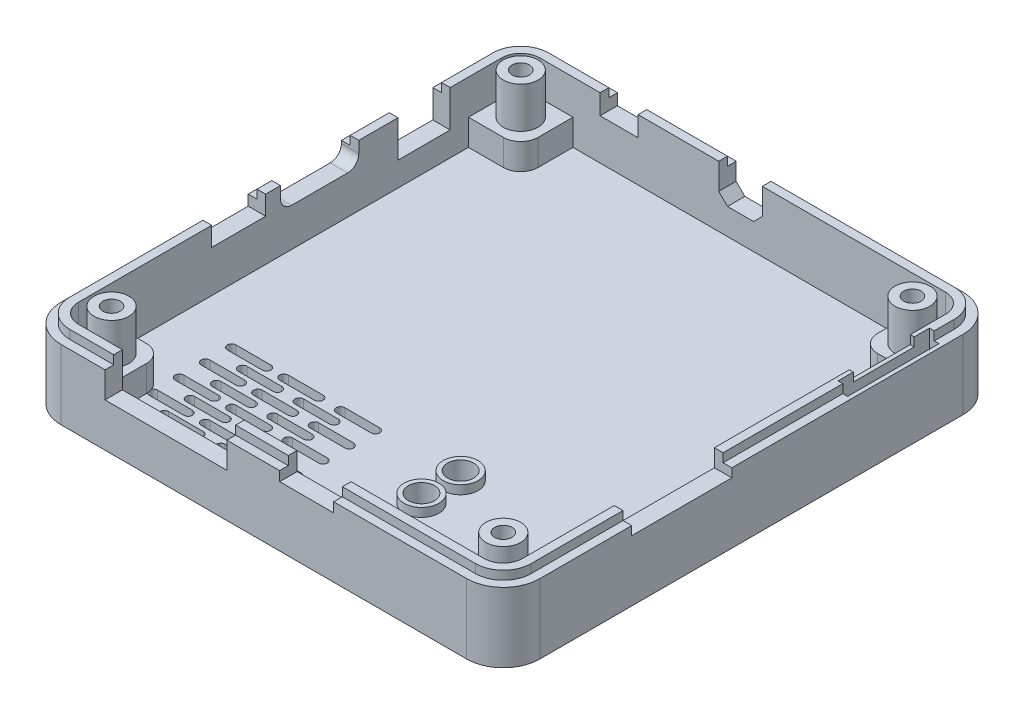
SolidWorks part; units mm, degrees
ref_plane "Front Plane" through (0, 0, 0) normal (0, 0, 1) x (1, 0, 0)
ref_plane "Top Plane" through (0, 0, 0) normal (0, 1, 0) x (1, 0, 0)
ref_plane "Right Plane" through (0, 0, 0) normal (1, 0, 0) x (0, 0, -1)
sketch "Sketch1" plane through (0, 0, 0) normal (0, 1, 0) x (1, 0, 0)
  line L17 (-23.3, 27.5) -> (23.3, 27.5)
  line L18 (-23.3, 26.5) -> (23.3, 26.5)
  line L26 (-25.5, 24.3) -> (-25.5, -24.3)
  line L27 (-23.3, -26.5) -> (23.3, -26.5)
  line L28 (25.5, 24.3) -> (25.5, -24.3)
  line L29 (-25.5, 26.5) -> (25.5, -26.5) construction
  line L30 (-25.5, -26.5) -> (25.5, 26.5) construction
  line L31 (26.5, 24.3) -> (26.5, -24.3)
  line L32 (-23.3, -27.5) -> (23.3, -27.5)
  line L33 (-26.5, 24.3) -> (-26.5, -24.3)
  line L34 (-23.3, 28.5) -> (23.3, 28.5)
  line L35 (27.5, 24.3) -> (27.5, -24.3)
  line L36 (-23.3, -28.5) -> (23.3, -28.5)
  line L37 (-27.5, 24.3) -> (-27.5, -24.3)
  line L38 (-19.5, 26.5) -> (-19.5, 22.5)
  line L39 (-25.5, -20.5) -> (-21.5, -20.5)
  line L40 (19.5, -26.5) -> (19.5, -22.5)
  line L41 (-25.5, 20.5) -> (-21.5, 20.5)
  line L42 (-19.5, -22.5) -> (-19.5, -26.5)
  line L43 (21.5, -20.5) -> (25.5, -20.5)
  line L44 (19.5, 22.5) -> (19.5, 26.5)
  line L45 (21.5, 20.5) -> (25.5, 20.5)
  arc A32 (25.5, -24.3) -> (23.3, -26.5) centre (23.3, -24.3) cw
  arc A33 (-23.3, -26.5) -> (-25.5, -24.3) centre (-23.3, -24.3) cw
  arc A34 (25.5, 24.3) -> (23.3, 26.5) centre (23.3, 24.3) ccw
  arc A35 (-23.3, 26.5) -> (-25.5, 24.3) centre (-23.3, 24.3) ccw
  arc A36 (26.5, 24.3) -> (23.3, 27.5) centre (23.3, 24.3) ccw
  arc A37 (26.5, -24.3) -> (23.3, -27.5) centre (23.3, -24.3) cw
  arc A38 (-23.3, -27.5) -> (-26.5, -24.3) centre (-23.3, -24.3) cw
  arc A39 (-23.3, 27.5) -> (-26.5, 24.3) centre (-23.3, 24.3) ccw
  arc A40 (27.5, 24.3) -> (23.3, 28.5) centre (23.3, 24.3) ccw
  arc A41 (27.5, -24.3) -> (23.3, -28.5) centre (23.3, -24.3) cw
  arc A42 (-23.3, -28.5) -> (-27.5, -24.3) centre (-23.3, -24.3) cw
  arc A43 (-23.3, 28.5) -> (-27.5, 24.3) centre (-23.3, 24.3) ccw
  circle A44 centre (-22.5, 23.5) radius 1
  circle A45 centre (22.5, 23.5) radius 1
  circle A46 centre (-22.5, -23.5) radius 1
  circle A47 centre (22.5, -23.5) radius 1
  arc A48 (19.5, 22.5) -> (21.5, 20.5) centre (21.5, 22.5) ccw
  arc A49 (21.5, -20.5) -> (19.5, -22.5) centre (21.5, -22.5) ccw
  arc A50 (-19.5, -22.5) -> (-21.5, -20.5) centre (-21.5, -22.5) ccw
  arc A51 (-19.5, 22.5) -> (-21.5, 20.5) centre (-21.5, 22.5) cw
  point P0 (0, 0)
  point P63 (19.5, 20.5)
  point P66 (19.5, -20.5)
  point P70 (-19.5, -20.5)
  point P73 (-19.5, 20.5)
  dimension "D3" = 2.2
  dimension "D14" = 3
  dimension "D17" = 3
  dimension "D18" = 2
  dimension "D19" = 2
  dimension "D28" = 6
  dimension "D10" = 3
  dimension "D11" = 3
  dimension "D12" = 3
  dimension "D13" = 3
  dimension "D15" = 3
  dimension "D16" = 3
  dimension "D20" = 2
  dimension "D21" = 2
  dimension "D30" = 2
  dimension "D1" = 51
  dimension "D2" = 53
  dimension "D4" = 1
  dimension "D5" = 1
  dimension "D6" = 53
  dimension "D7" = 55
  dimension "D8" = 55
  dimension "D9" = 57
  dimension "D22" = 6
  dimension "D23" = 6
  dimension "D24" = 6
  dimension "D25" = 6
  dimension "D26" = 6
  dimension "D27" = 6
  dimension "D29" = 6
extrude "Boss-Extrude1" add sketch "Sketch1" along normal blind 8 contours L34 A43 L37 A42 L36 A41 L35 A40 A39 L17 A36 L31 A37 L32 A38 L33 region at (0, 0, -27.7079)
extrude "Boss-Extrude2" add sketch "Sketch1<3>" along normal blind 9 contours L17 A39 L33 A38 L32 A37 L31 A36 A35 L18 A34 L28 A32 L27 A33 L26 region at (0, 0, -26.7362)
sketch "Sketch1<3>" plane through (0, 0, 0) normal (0, 1, 0) x (1, 0, 0) same geometry as "Sketch1"
extrude "Boss-Extrude3" add sketch "Sketch1<4>" along normal blind 2 contours L38 A51 L41 L26 L39 A50 L42 L27 L40 A49 L43 L28 L45 A48 L44 L18 region at (0, 0, 0)
sketch "Sketch1<4>" plane through (0, 0, 0) normal (0, 1, 0) x (1, 0, 0) same geometry as "Sketch1"
extrude "Boss-Extrude4" add sketch "Sketch1<5>" along normal blind 5 contours A51 L38 L18 A35 L26 L41 A44 | L42 A50 L39 L26 A33 L27 A46 | L43 A49 L40 L27 A32 L28 A47 | L44 A48 L45 L28 A34 L18 A45 | A44 | A45 | A47 | A46 region at (-21.4, 0, -26.4151) region at (21.4, 0, -26.4151) region at (-23.5, 0, 20.5849) region at (25.4151, 0, 22.4)
sketch "Sketch1<5>" plane through (0, 0, 0) normal (0, 1, 0) x (1, 0, 0) same geometry as "Sketch1"
sketch "Sketch2" plane through (0, 5, 0) normal (0, 1, 0) x (1, 0, 0)
  circle A0 centre (-22.5, 23.5) radius 1
  circle A1 centre (22.5, 23.5) radius 1
  circle A2 centre (22.5, -23.5) radius 1
  circle A3 centre (-22.5, -23.5) radius 1
  circle A4 centre (-22.5, -23.5) radius 2
  circle A5 centre (22.5, -23.5) radius 2
  circle A6 centre (22.5, 23.5) radius 2
  circle A7 centre (-22.5, 23.5) radius 2
  dimension "D1" = 2
  dimension "D2" = 4
  dimension "D3" = 2
  dimension "D4" = 4
  dimension "D5" = 2
  dimension "D6" = 4
  dimension "D7" = 2
  dimension "D8" = 4
extrude "Boss-Extrude5" add sketch "Sketch2" along normal blind 4.7
sketch "Sketch3" plane through (-27.5, 0, 0) normal (-1, 0, 0) x (0, 0, 1)
  line L0 (-24.3, 9) -> (24.3, 9) construction
  line L1 (-18.4, 9) -> (-12.4, 9)
  line L2 (-18.4, 9) -> (-18.4, 4.78)
  line L3 (-18.4, 4.78) -> (-12.4, 4.78)
  line L4 (-12.4, 9) -> (-12.4, 4.78)
  line L6 (-7.9, 9) -> (1.1, 9)
  line L7 (-7.9, 9) -> (-7.9, 7.68)
  line L8 (-6.62, 6.4) -> (-0.18, 6.4)
  line L9 (1.1, 9) -> (1.1, 7.68)
  line L10 (2.8, 9) -> (9, 9)
  line L11 (2.8, 9) -> (2.8, 6.8)
  line L12 (2.8, 6.8) -> (9, 6.8)
  line L13 (9, 9) -> (9, 6.8)
  line L14 (28.5, 8) -> (28.5, 0) construction
  line L15 (-28.5, 8) -> (-28.5, 0) construction
  arc A0 (1.1, 7.68) -> (-0.18, 6.4) centre (-0.18, 7.68) cw
  arc A1 (-6.62, 6.4) -> (-7.9, 7.68) centre (-6.62, 7.68) cw
  point P20 (1.1, 6.4)
  point P23 (-7.9, 6.4)
  dimension "D11" = 1.28
  dimension "D1" = 6
  dimension "D2" = 4.22
  dimension "D3" = 4.5
  dimension "D4" = 9
  dimension "D5" = 1.7
  dimension "D6" = 6.2
  dimension "D7" = 2.6
  dimension "D8" = 2.2
  dimension "D9" = 27.4
  dimension "D10" = 20.6
extrude "Cut-Extrude1" cut sketch "Sketch3" against normal blind 2
sketch "Sketch5" plane through (0, 0, -28.5) normal (0, 0, -1) x (-1, 0, 0)
  line L0 (0, 0) -> (0, 21.9509) construction
  line L1 (23.3, 9) -> (-23.3, 9) construction
  line L2 (1.75, 5) -> (-1.25, 5)
  line L3 (2.75, 6) -> (2.75, 9)
  line L4 (2.75, 9) -> (-2.25, 9)
  line L5 (-2.25, 6) -> (-2.25, 9)
  line L6 (2.75, 5) -> (-2.25, 9) construction
  line L7 (2.75, 9) -> (-2.25, 5) construction
  line L8 (-1.25, 5) -> (-2.25, 6)
  line L9 (2.75, 6) -> (1.75, 5)
  line L10 (27.5, 8) -> (27.5, 0) construction
  line L11 (12.02, 9) -> (16.38, 9)
  line L12 (12.02, 9) -> (12.02, 6.7)
  line L13 (12.02, 6.7) -> (16.38, 6.7)
  line L14 (16.38, 9) -> (16.38, 6.7)
  point P3 (0.25, 7)
  dimension "D1" = 0.25
  dimension "D2" = 4
  dimension "D3" = 5
  dimension "D4" = 2.3
  dimension "D5" = 4.36
  dimension "D6" = 11.12
extrude "Cut-Extrude3" cut sketch "Sketch5" against normal blind 2
sketch "Sketch6" plane through (0, 9, 0) normal (0, 1, 0) x (1, 0, 0)
  line L0 (21.5, 20.5) -> (25.5, 20.5) construction
  line L1 (25.95, 22) -> (27.05, 22)
  line L2 (25.95, 22) -> (25.95, 11.5)
  line L3 (25.95, 11.5) -> (27.05, 11.5)
  line L4 (27.05, 22) -> (27.05, 11.5)
  line L5 (25.5, 24.3) -> (25.5, -24.3) construction
  line L6 (27.5, 24.3) -> (27.5, -24.3) construction
  dimension "D1" = 1.5
  dimension "D2" = 10.5
  dimension "D3" = 1.1
  dimension "D4" = 0.45
  dimension "D5" = 0.45
extrude "Cut-Extrude4" cut sketch "Sketch6" against normal blind 3
sketch "Sketch7" plane through (27.5, 0, 0) normal (1, 0, 0) x (0, 0, -1)
  line L0 (22, 9) -> (11.5, 9) construction
  line L1 (13.25, 9) -> (20.25, 9)
  line L2 (13.25, 9) -> (13.25, 8)
  line L3 (13.25, 8) -> (20.25, 8)
  line L4 (20.25, 9) -> (20.25, 8)
  line L5 (28.5, 8) -> (28.5, 0) construction
  line L6 (11.5, 9) -> (-24.3, 9) construction
  line L7 (-13.75, 9) -> (-2.25, 9)
  line L8 (-13.75, 9) -> (-13.75, 7)
  line L9 (-13.75, 7) -> (-2.25, 7)
  line L10 (-2.25, 9) -> (-2.25, 7)
  line L11 (-28.5, 8) -> (-28.5, 0) construction
  dimension "D1" = 1
  dimension "D2" = 7
  dimension "D3" = 8.25
  dimension "D4" = 14.75
  dimension "D5" = 11.5
  dimension "D6" = 2
extrude "Cut-Extrude5" cut sketch "Sketch7" against normal blind 2
sketch "Sketch9" plane through (0, 0, 28.5) normal (0, 0, 1) x (1, 0, 0)
  line L0 (-23.3, 9) -> (23.3, 9) construction
  line L1 (-18.25, 9) -> (-4.25, 9)
  line L2 (-18.25, 9) -> (-18.25, 5)
  line L3 (-18.25, 5) -> (-4.25, 5)
  line L4 (-4.25, 9) -> (-4.25, 5)
  line L5 (-27.5, 8) -> (-27.5, 0) construction
  line L6 (1.81, 9) -> (8.01, 9)
  line L7 (1.81, 9) -> (1.81, 6.9)
  line L8 (1.81, 6.9) -> (8.01, 6.9)
  line L9 (8.01, 9) -> (8.01, 6.9)
  point P10 (1.81, 7.95)
  dimension "D1" = 4
  dimension "D2" = 14
  dimension "D3" = 6.06
  dimension "D4" = 6.2
  dimension "D5" = 2.1
  dimension "D6" = 9.25
extrude "Cut-Extrude6" cut sketch "Sketch9" against normal blind 2
sketch "Sketch10" plane through (0, 0, 0) normal (0, -1, 0) x (1, 0, 0)
  line L0 (-23.3, 28.5) -> (23.3, 28.5) construction
  line L1 (27.5, -24.3) -> (27.5, 24.3) construction
  circle A0 centre (7.2, 17.6) radius 1.5
  circle A1 centre (7.2, 13.1) radius 1.5
  dimension "D1" = 3
  dimension "D2" = 3
  dimension "D3" = 4.5
  dimension "D4" = 10.9
  dimension "D5" = 20.3
  dimension "D6" = 15.4
extrude "Cut-Extrude7" cut sketch "Sketch10" against normal blind 2
sketch "Sketch11" plane through (0, 0, 0) normal (0, -1, 0) x (1, 0, 0)
  line L0 (-20.7881, 19) -> (-2.0875, 19) construction
  line L1 (-11.2, 23.9809) -> (-11.2, 13.932) construction
  line L3 (-23.3, 28.5) -> (23.3, 28.5) construction
  line L8 (-13.2, 19.5) -> (-9.2, 19.5)
  line L14 (-13.2, 18.5) -> (-9.2, 18.5)
  line L16 (-13.2, 19.5) -> (-9.2, 18.5) construction
  line L17 (-13.2, 18.5) -> (-9.2, 19.5) construction
  line L18 (-27.5, -24.3) -> (-27.5, 24.3) construction
  line L19 (-6.7, 19.5) -> (-2.7, 19.5)
  line L20 (-6.7, 18.5) -> (-2.7, 18.5)
  line L21 (-6.7, 19.5) -> (-2.7, 18.5) construction
  line L22 (-6.7, 18.5) -> (-2.7, 19.5) construction
  line L23 (-19.2, 19.5) -> (-15.2, 19.5)
  line L24 (-19.2, 18.5) -> (-15.2, 18.5)
  line L25 (-19.2, 19.5) -> (-15.2, 18.5) construction
  line L26 (-19.2, 18.5) -> (-15.2, 19.5) construction
  line L27 (-16.45, 21) -> (-12.45, 21)
  line L28 (-16.45, 20) -> (-12.45, 20)
  line L29 (-16.45, 21) -> (-12.45, 20) construction
  line L30 (-16.45, 20) -> (-12.45, 21) construction
  line L31 (-9.95, 21) -> (-5.95, 21)
  line L32 (-9.95, 20) -> (-5.95, 20)
  line L33 (-9.95, 21) -> (-5.95, 20) construction
  line L34 (-9.95, 20) -> (-5.95, 21) construction
  line L35 (-9.95, 18) -> (-5.95, 17) construction
  line L36 (-9.95, 17) -> (-5.95, 18) construction
  line L37 (-16.45, 18) -> (-12.45, 17) construction
  line L38 (-16.45, 17) -> (-12.45, 18) construction
  line L39 (-9.95, 18) -> (-5.95, 18)
  line L40 (-9.95, 17) -> (-5.95, 17)
  line L41 (-16.45, 18) -> (-12.45, 18)
  line L42 (-16.45, 17) -> (-12.45, 17)
  line L43 (-18.8854, 20.5) -> (-4.597, 20.5) construction
  line L44 (-19.0364, 17.5) -> (-3.4772, 17.5) construction
  line L45 (-19.2, 22.5) -> (-15.2, 21.5) construction
  line L46 (-19.2, 21.5) -> (-15.2, 22.5) construction
  line L47 (-6.7, 22.5) -> (-2.7, 21.5) construction
  line L48 (-6.7, 21.5) -> (-2.7, 22.5) construction
  line L49 (-13.2, 22.5) -> (-9.2, 21.5) construction
  line L50 (-13.2, 21.5) -> (-9.2, 22.5) construction
  line L51 (-19.2, 22.5) -> (-15.2, 22.5)
  line L52 (-19.2, 21.5) -> (-15.2, 21.5)
  line L53 (-6.7, 22.5) -> (-2.7, 22.5)
  line L54 (-6.7, 21.5) -> (-2.7, 21.5)
  line L55 (-13.2, 22.5) -> (-9.2, 22.5)
  line L56 (-13.2, 21.5) -> (-9.2, 21.5)
  line L57 (-19.2, 16.5) -> (-15.2, 15.5) construction
  line L58 (-19.2, 15.5) -> (-15.2, 16.5) construction
  line L59 (-6.7, 16.5) -> (-2.7, 15.5) construction
  line L60 (-6.7, 15.5) -> (-2.7, 16.5) construction
  line L61 (-13.2, 16.5) -> (-9.2, 15.5) construction
  line L62 (-13.2, 15.5) -> (-9.2, 16.5) construction
  line L63 (-19.2, 16.5) -> (-15.2, 16.5)
  line L64 (-19.2, 15.5) -> (-15.2, 15.5)
  line L65 (-6.7, 16.5) -> (-2.7, 16.5)
  line L66 (-6.7, 15.5) -> (-2.7, 15.5)
  line L67 (-13.2, 16.5) -> (-9.2, 16.5)
  line L68 (-13.2, 15.5) -> (-9.2, 15.5)
  line L69 (-21.1922, 22) -> (-1.31, 22) construction
  line L70 (-20.7881, 16) -> (-2.0875, 16) construction
  line L71 (-9.95, 24) -> (-5.95, 23) construction
  line L72 (-9.95, 23) -> (-5.95, 24) construction
  line L73 (-16.45, 24) -> (-12.45, 23) construction
  line L74 (-16.45, 23) -> (-12.45, 24) construction
  line L75 (-9.95, 24) -> (-5.95, 24)
  line L76 (-9.95, 23) -> (-5.95, 23)
  line L77 (-16.45, 24) -> (-12.45, 24)
  line L78 (-16.45, 23) -> (-12.45, 23)
  line L79 (-16.45, 15) -> (-12.45, 14) construction
  line L80 (-16.45, 14) -> (-12.45, 15) construction
  line L81 (-9.95, 15) -> (-5.95, 14) construction
  line L82 (-9.95, 14) -> (-5.95, 15) construction
  line L83 (-16.45, 15) -> (-12.45, 15)
  line L84 (-16.45, 14) -> (-12.45, 14)
  line L85 (-9.95, 15) -> (-5.95, 15)
  line L86 (-9.95, 14) -> (-5.95, 14)
  line L87 (-19.2, 23.5) -> (-3.6634, 23.5) construction
  line L88 (-13.2, 25.5) -> (-9.2, 24.5) construction
  line L89 (-13.2, 24.5) -> (-9.2, 25.5) construction
  line L90 (-6.7, 25.5) -> (-2.7, 24.5) construction
  line L91 (-6.7, 24.5) -> (-2.7, 25.5) construction
  line L92 (-19.2, 25.5) -> (-15.2, 24.5) construction
  line L93 (-19.2, 24.5) -> (-15.2, 25.5) construction
  line L94 (-13.2, 25.5) -> (-9.2, 25.5)
  line L95 (-13.2, 24.5) -> (-9.2, 24.5)
  line L96 (-6.7, 25.5) -> (-2.7, 25.5)
  line L97 (-6.7, 24.5) -> (-2.7, 24.5)
  line L98 (-19.2, 25.5) -> (-15.2, 25.5)
  line L99 (-19.2, 24.5) -> (-15.2, 24.5)
  line L100 (-20.5381, 14.5) -> (-1.8375, 14.5) construction
  line L101 (-13.2, 13.5) -> (-9.2, 12.5) construction
  line L102 (-13.2, 12.5) -> (-9.2, 13.5) construction
  line L103 (-6.7, 13.5) -> (-2.7, 12.5) construction
  line L104 (-6.7, 12.5) -> (-2.7, 13.5) construction
  line L105 (-19.2, 13.5) -> (-15.2, 12.5) construction
  line L106 (-19.2, 12.5) -> (-15.2, 13.5) construction
  line L107 (-13.2, 13.5) -> (-9.2, 13.5)
  line L108 (-13.2, 12.5) -> (-9.2, 12.5)
  line L109 (-6.7, 13.5) -> (-2.7, 13.5)
  line L110 (-6.7, 12.5) -> (-2.7, 12.5)
  line L111 (-19.2, 13.5) -> (-15.2, 13.5)
  line L112 (-19.2, 12.5) -> (-15.2, 12.5)
  arc A35 (-13.2, 19.5) -> (-13.2, 18.5) centre (-13.2, 19) ccw
  arc A36 (-9.2, 19.5) -> (-9.2, 18.5) centre (-9.2, 19) cw
  arc A37 (-6.7, 19.5) -> (-6.7, 18.5) centre (-6.7, 19) ccw
  arc A38 (-2.7, 19.5) -> (-2.7, 18.5) centre (-2.7, 19) cw
  arc A39 (-19.2, 19.5) -> (-19.2, 18.5) centre (-19.2, 19) ccw
  arc A40 (-15.2, 19.5) -> (-15.2, 18.5) centre (-15.2, 19) cw
  arc A41 (-16.45, 21) -> (-16.45, 20) centre (-16.45, 20.5) ccw
  arc A42 (-12.45, 21) -> (-12.45, 20) centre (-12.45, 20.5) cw
  arc A43 (-9.95, 21) -> (-9.95, 20) centre (-9.95, 20.5) ccw
  arc A44 (-5.95, 21) -> (-5.95, 20) centre (-5.95, 20.5) cw
  arc A45 (-5.95, 17) -> (-5.95, 18) centre (-5.95, 17.5) ccw
  arc A46 (-9.95, 17) -> (-9.95, 18) centre (-9.95, 17.5) cw
  arc A47 (-12.45, 17) -> (-12.45, 18) centre (-12.45, 17.5) ccw
  arc A48 (-16.45, 17) -> (-16.45, 18) centre (-16.45, 17.5) cw
  arc A49 (-15.2, 21.5) -> (-15.2, 22.5) centre (-15.2, 22) ccw
  arc A50 (-19.2, 21.5) -> (-19.2, 22.5) centre (-19.2, 22) cw
  arc A51 (-2.7, 21.5) -> (-2.7, 22.5) centre (-2.7, 22) ccw
  arc A52 (-6.7, 21.5) -> (-6.7, 22.5) centre (-6.7, 22) cw
  arc A53 (-9.2, 21.5) -> (-9.2, 22.5) centre (-9.2, 22) ccw
  arc A54 (-13.2, 21.5) -> (-13.2, 22.5) centre (-13.2, 22) cw
  arc A55 (-15.2, 15.5) -> (-15.2, 16.5) centre (-15.2, 16) ccw
  arc A56 (-19.2, 15.5) -> (-19.2, 16.5) centre (-19.2, 16) cw
  arc A57 (-2.7, 15.5) -> (-2.7, 16.5) centre (-2.7, 16) ccw
  arc A58 (-6.7, 15.5) -> (-6.7, 16.5) centre (-6.7, 16) cw
  arc A59 (-9.2, 15.5) -> (-9.2, 16.5) centre (-9.2, 16) ccw
  arc A60 (-13.2, 15.5) -> (-13.2, 16.5) centre (-13.2, 16) cw
  arc A61 (-5.95, 23) -> (-5.95, 24) centre (-5.95, 23.5) ccw
  arc A62 (-9.95, 23) -> (-9.95, 24) centre (-9.95, 23.5) cw
  arc A63 (-12.45, 23) -> (-12.45, 24) centre (-12.45, 23.5) ccw
  arc A64 (-16.45, 23) -> (-16.45, 24) centre (-16.45, 23.5) cw
  arc A65 (-16.45, 15) -> (-16.45, 14) centre (-16.45, 14.5) ccw
  arc A66 (-12.45, 15) -> (-12.45, 14) centre (-12.45, 14.5) cw
  arc A67 (-9.95, 15) -> (-9.95, 14) centre (-9.95, 14.5) ccw
  arc A68 (-5.95, 15) -> (-5.95, 14) centre (-5.95, 14.5) cw
  arc A69 (-13.2, 25.5) -> (-13.2, 24.5) centre (-13.2, 25) ccw
  arc A70 (-9.2, 25.5) -> (-9.2, 24.5) centre (-9.2, 25) cw
  arc A71 (-6.7, 25.5) -> (-6.7, 24.5) centre (-6.7, 25) ccw
  arc A72 (-2.7, 25.5) -> (-2.7, 24.5) centre (-2.7, 25) cw
  arc A73 (-19.2, 25.5) -> (-19.2, 24.5) centre (-19.2, 25) ccw
  arc A74 (-15.2, 25.5) -> (-15.2, 24.5) centre (-15.2, 25) cw
  arc A75 (-13.2, 13.5) -> (-13.2, 12.5) centre (-13.2, 13) ccw
  arc A76 (-9.2, 13.5) -> (-9.2, 12.5) centre (-9.2, 13) cw
  arc A77 (-6.7, 13.5) -> (-6.7, 12.5) centre (-6.7, 13) ccw
  arc A78 (-2.7, 13.5) -> (-2.7, 12.5) centre (-2.7, 13) cw
  arc A79 (-19.2, 13.5) -> (-19.2, 12.5) centre (-19.2, 13) ccw
  arc A80 (-15.2, 13.5) -> (-15.2, 12.5) centre (-15.2, 13) cw
  point P0 (-11.2, 19)
  point P11 (-14.45, 20.5)
  point P12 (-17.2, 19)
  point P13 (-4.7, 19)
  point P33 (-7.95, 20.5)
  point P55 (-7.95, 17.5)
  point P56 (-14.45, 17.5)
  point P79 (-4.7, 22)
  point P80 (-17.2, 22)
  point P81 (-11.2, 22)
  point P100 (-4.7, 16)
  point P101 (-17.2, 16)
  point P102 (-11.2, 16)
  point P119 (-7.95, 23.5)
  point P120 (-14.45, 23.5)
  point P133 (-14.45, 14.5)
  point P134 (-7.95, 14.5)
  point P155 (-11.2, 25)
  point P156 (-17.2, 25)
  point P157 (-4.7, 25)
  point P178 (-11.2, 13)
  point P179 (-17.2, 13)
  point P180 (-4.7, 13)
  dimension "D1" = 9.5
  dimension "D2" = 16.3
  dimension "D3" = 1
  dimension "D4" = 0.5
  dimension "D5" = 4
  dimension "D6" = 2
  dimension "D8" = 2
  dimension "D12" = 2.5
  dimension "D13" = 2.5
  dimension "D14" = 4
  dimension "D15" = 4
  dimension "D16" = 1.25
  dimension "D7" = 2
  dimension "D9" = 1
  dimension "D11" = 1
  dimension "D17" = 1.25
  dimension "D10" = 2
extrude "Cut-Extrude8" cut sketch "Sketch11" against normal blind 2
sketch "Sketch12" plane through (0, 2, 0) normal (0, 1, 0) x (1, 0, 0)
  circle A0 centre (7.2, -13.1) radius 1.5
  circle A1 centre (7.2, -13.1) radius 2
  circle A2 centre (7.2, -17.6) radius 1.5
  circle A3 centre (7.2, -17.6) radius 2
  dimension "D1" = 4
  dimension "D2" = 3
  dimension "D3" = 3
  dimension "D4" = 4
extrude "Boss-Extrude7" add sketch "Sketch12" along normal blind 1
